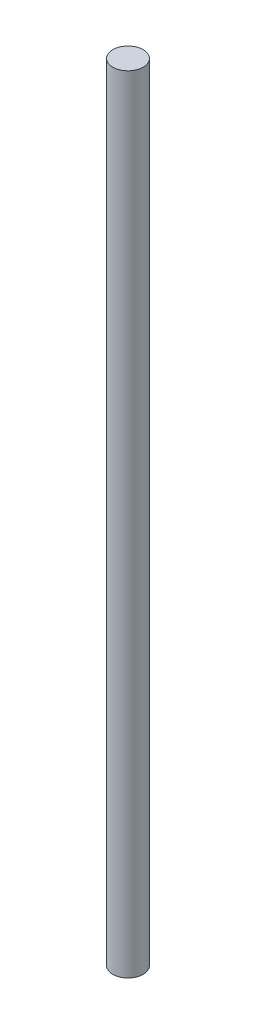
SolidWorks part; units mm, degrees
ref_plane "Front" through (0, 0, 0) normal (0, 0, 1) x (1, 0, 0)
ref_plane "Top" through (0, 0, 0) normal (0, 1, 0) x (1, 0, 0)
ref_plane "Right" through (0, 0, 0) normal (1, 0, 0) x (0, 0, -1)
sketch "Sketch1" plane through (0, 0, 0) normal (0, 1, 0) x (1, 0, 0)
  circle A0 centre (0, 0) radius 2.3327
  circle A1 centre (0, 0) radius 2.3327 construction
extrude "Boss-Extrude1" add sketch "Sketch1" against normal up to surface (109.6556 mm away)
extrude "Boss-Extrude3" add sketch "Sketch1<2>" along normal up to surface (11 mm away)
sketch "Sketch1<2>" plane through (0, 0, 0) normal (0, 1, 0) x (1, 0, 0) same geometry as "Sketch1"
